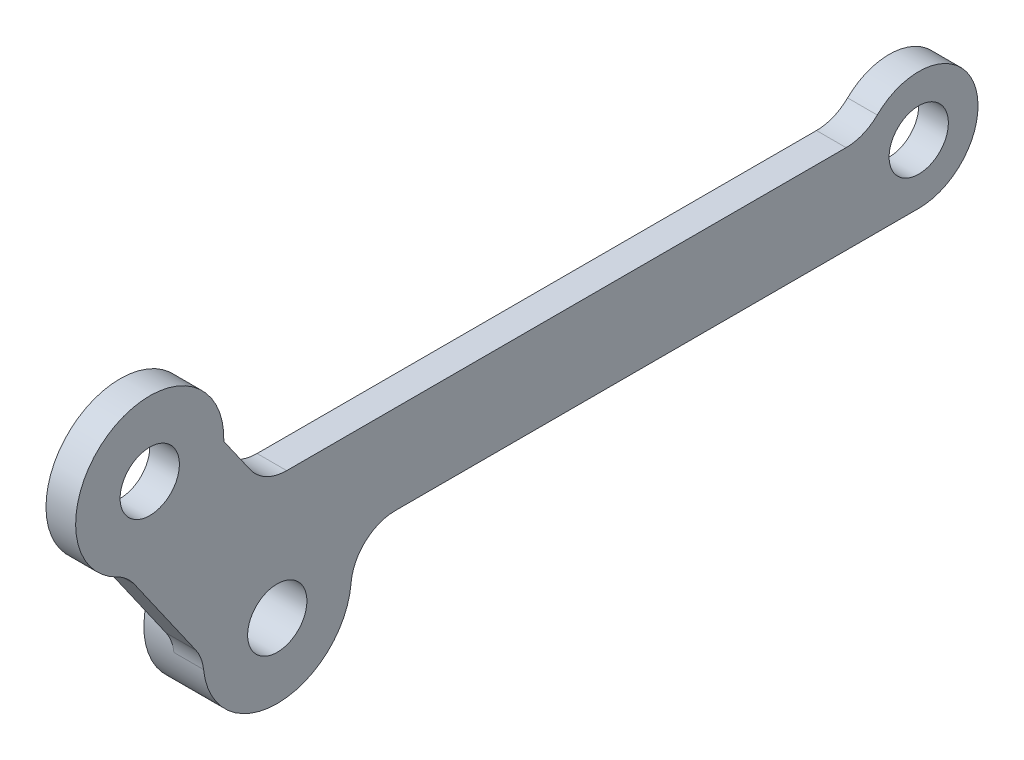
SolidWorks part; units mm, degrees
ref_plane "前视基准面" through (0, 0, 0) normal (0, 0, 1) x (1, 0, 0)
ref_plane "上视基准面" through (0, 0, 0) normal (0, 1, 0) x (1, 0, 0)
ref_plane "右视基准面" through (0, 0, 0) normal (1, 0, 0) x (0, 0, -1)
other "Configuration Table"
sketch "草图1" plane through (0, 0, 0) normal (1, 0, 0) x (0, 0, -1)
  line L1 (0, 0) -> (44.2012, 0)
  line L2 (0, 0) -> (4.2012, -6)
  line L3 (4.2012, -6) -> (44.2012, -6)
  line L4 (44.2012, 0) -> (44.2012, -6)
  line L5 (-10.9556, 1.6987) -> (-4.4024, 6.2873)
  line L6 (-10.9556, 1.6987) -> (-2.352, -10.5886)
  line L7 (-2.352, -10.5886) -> (4.2012, -6)
  line L8 (-4.4024, 6.2873) -> (4.2012, -6)
  circle A0 centre (-7.679, 3.993) radius 5
  circle A1 centre (0.9246, -8.2943) radius 5
  circle A3 centre (44.2012, -2) radius 4
  circle A4 centre (-7.679, 3.993) radius 2
  circle A5 centre (44.2012, -2) radius 2
  circle A6 centre (0.9246, -8.2943) radius 2
  dimension "D5" = 10
  dimension "D6" = 10
  dimension "D8" = 8
  dimension "D9" = 4
  dimension "D1" = 125
  dimension "D2" = 40
  dimension "D3" = 6
  dimension "D4" = 8
  dimension "D7" = 15
extrude "凸台-拉伸1" add sketch "草图1" along normal blind 2 contours A3 L1 L2 A1 L3 | A0 | L8 L5 L6 L7 | A1 | A3 region at (0, -2.9524, -21.636)
extrude "凸台-拉伸2" add sketch "草图1<4>" against normal blind 2 contours A1
sketch "草图1<4>" plane through (0, 0, 0) normal (1, 0, 0) x (0, 0, -1) same geometry as "草图1"
extrude "切除-拉伸1" cut sketch "草图1<3>" along normal through all both and the other way through all contours A4 | A6 | A5
sketch "草图1<3>" plane through (0, 0, 0) normal (1, 0, 0) x (0, 0, -1) same geometry as "草图1"
fillet "圆角1" radius 3 5 edges at (1, 0, -40.7371) (1, -8.1312, 4.0727) (1, -0.7588, 9.2349) (1, -6, -5.3672) (1, 0, 0)
